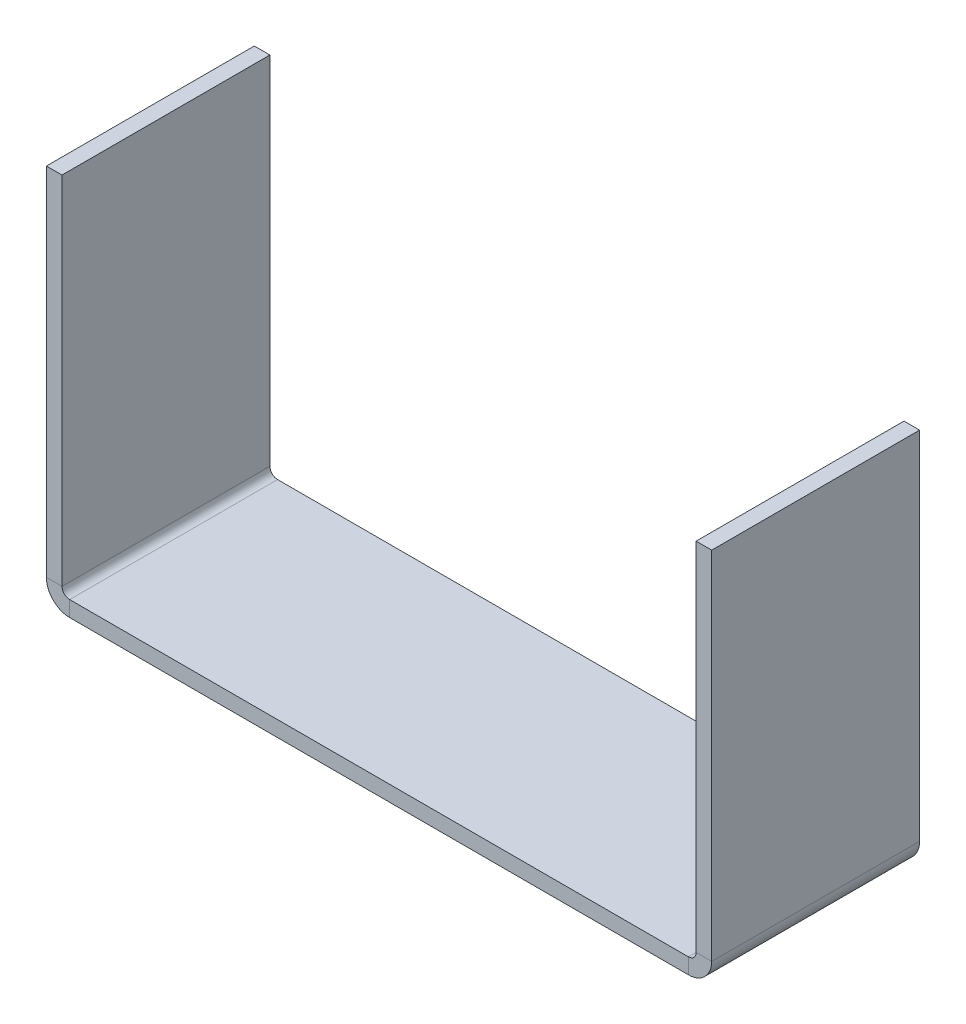
SolidWorks part; units mm, degrees
note: The reader was unsure of these and kept them because the rebuilt part matched: flange length of "Ребро-кромка1", "Ребро-кромка2".
ref_plane "Спереди" through (0, 0, 0) normal (0, 0, 1) x (1, 0, 0)
ref_plane "Сверху" through (0, 0, 0) normal (0, 1, 0) x (1, 0, 0)
ref_plane "Справа" through (0, 0, 0) normal (1, 0, 0) x (0, 0, -1)
sketch "Эскиз1" plane through (0, 0, 0) normal (0, 1, 0) x (1, 0, 0)
  line L1 (0, 0) -> (64, 0)
  line L2 (0, 0) -> (0, 20)
  line L3 (0, 20) -> (64, 20)
  line L4 (64, 0) -> (64, 20)
base flange "Базовая кромка1" sketch "Эскиз1" thickness 1.5 reverse thickness direction no parameters "D1"=0.7366
edge flange "Ребро-кромка1" sketch "Эскиз8" flange angle 90 flange length 36.5 flange position material inside bend radius 0.7366 thickness 1.5 relief rectangular parameters "D6"=10
sketch "Эскиз8" plane through (0, 0, 0) normal (-1, 0, 0) x (0, 0, 1)
  line L0 (-20, 0) -> (0, 0) construction
  line L1 (-20, 0) -> (0, 0)
  line L2 (-20, 0) -> (-20, 35)
  line L3 (-20, 35) -> (0, 35)
  line L4 (0, 35) -> (0, 0)
bend "EdgeBend1" bend radius 0.7366 bend angle 90 parameters "D5"=1
edge flange "Ребро-кромка2" sketch "Эскиз11" flange angle 90 flange length 36.5 flange position material inside bend radius 0.7366 thickness 1.5 relief rectangular parameters "D6"=10
sketch "Эскиз11" plane through (64, 0, 0) normal (1, 0, 0) x (0, 0, -1)
  line L2 (0, 0) -> (0, 35)
  line L3 (0, 35) -> (20, 35)
  line L4 (20, 35) -> (20, 0)
  line L7 (0, 0) -> (20, 0) construction
  line L8 (0, 0) -> (20, 0)
bend "EdgeBend2" bend radius 0.7366 bend angle 90 parameters "D5"=2
sketch "Сгиб-Линии1" [suppressed] plane through (0, 0, 0) normal (0, 1, 0) x (1, 0, 0)
sketch "Граничная рамка1" [suppressed] plane through (0, 0, 0) normal (0, 1, 0) x (1, 0, 0)
sheet metal parameters "Листовой металл1" thickness 1.5 parameters "D1"=0.7366
flat pattern "Развертка1" [suppressed]
sketch "Сгиб-Линии2" plane through (0, 0, 0) normal (0, 1, 0) x (1, 0, 0)
sketch3d "Граничная рамка2" [suppressed]
  line L0 (-200, 20, 0) -> (0, 20, 0) construction
  line L1 (-200, 0, 0) -> (0, 0, 0) construction
  line L2 (-200, 20, 0) -> (-200, 0, 0) construction
  line L3 (0, 20, 0) -> (0, 0, 0) construction
sheet metal parameters "Листовой металл2" thickness 1.5 parameters "D1"=0.7366
flat pattern "Развертка1"
sketch "Сгиб-Линии2" plane through (0, 0, 0) normal (0, 1, 0) x (1, 0, 0)
  line L0 (1.069, 20) -> (1.069, 0) construction
  line L1 (1.069, 20) -> (1.069, 0) construction
sketch3d "Граничная рамка2" [suppressed]
  line L0 (200, 20, 0) -> (-30.5985, 20, 0) construction
  line L1 (200, 0, 0) -> (-30.5985, 0, 0) construction
  line L2 (200, 20, 0) -> (200, 0, 0) construction
  line L3 (-30.5985, 20, 0) -> (-30.5985, 0, 0) construction
bend of the flat pattern "Плоское состояние-<EdgeBend1>1"
sheet metal parameters "Листовой металл3" thickness 1.5 parameters "D1"=0.7366
flat pattern "Развертка1"
sketch "Сгиб-Линии2" plane through (0, 0, 0) normal (0, 1, 0) x (1, 0, 0)
  line L0 (1.069, 20) -> (1.069, 0) construction
  line L1 (1.069, 20) -> (1.069, 0) construction
  line L2 (48.931, 0) -> (48.931, 20) construction
  line L3 (48.931, 0) -> (48.931, 20) construction
sketch3d "Граничная рамка2" [suppressed]
  line L0 (84.3619, 20, 0) -> (-34.3619, 20, 0) construction
  line L1 (84.3619, 0, 0) -> (-34.3619, 0, 0) construction
  line L2 (84.3619, 20, 0) -> (84.3619, 0, 0) construction
  line L3 (-34.3619, 20, 0) -> (-34.3619, 0, 0) construction
bend of the flat pattern "Плоское состояние-<EdgeBend1>1"
bend of the flat pattern "Плоское состояние-<EdgeBend2>1"
